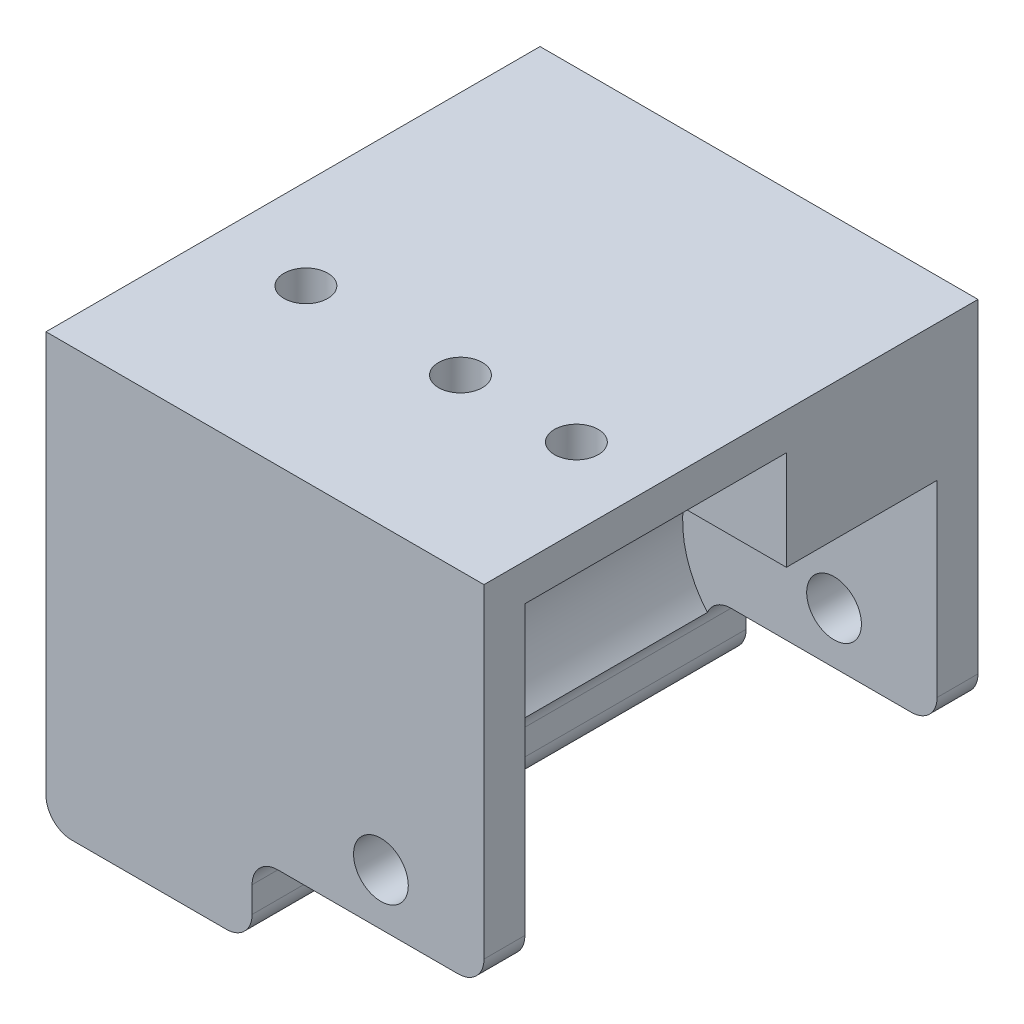
SolidWorks part; units mm, degrees
ref_plane "Front Plane" through (0, 0, 0) normal (0, 0, 1) x (1, 0, 0)
ref_plane "Top Plane" through (0, 0, 0) normal (0, 1, 0) x (1, 0, 0)
ref_plane "Right Plane" through (0, 0, 0) normal (1, 0, 0) x (0, 0, -1)
sketch "Sketch1" plane through (0, 0, 0) normal (0, 0, 1) x (1, 0, 0)
  line L0 (-18, 24) -> (-18, 0) construction
  line L5 (0, 0) -> (-18, 0)
  line L6 (0, 0) -> (0, 24)
  line L7 (0, 24) -> (-34, 24)
  line L8 (-34, 0) -> (-34, 24)
  line L11 (-34, 0) -> (-34, -6)
  line L12 (-34, -6) -> (-18, -6)
  line L13 (-18, 0) -> (-18, -6)
  circle A27 centre (-4, 19.15) radius 2.125 construction
  circle A28 centre (-12, 19.15) radius 2.125 construction
  circle A29 centre (-21, 19.15) radius 2.125 construction
  circle A30 centre (-8, 4) radius 2.125
  dimension "D3" = 4.25
  dimension "D7" = 8
  dimension "D8" = 4.25
  dimension "D1" = 4.25
  dimension "D2" = 4.25
  dimension "D4" = 4.85
  dimension "D5" = 9
  dimension "D9" = 4
  dimension "D6" = 4
  dimension "D10" = 4
  dimension "D11" = 24
  dimension "D12" = 13
  dimension "D13" = 16
  dimension "D14" = 30
extrude "Boss-Extrude1" add sketch "Sketch1" along normal blind 3.175
ref_plane "Plane1" through (0, 0, -16) normal (0, 0, -1) x (-1, 0, 0)
sketch "Sketch4" plane through (0, 24, 0) normal (0, 1, 0) x (1, 0, 0)
  line L0 (-34, 32) -> (0, 32) construction
  line L1 (-34, -3.175) -> (0, -3.175)
  line L2 (-34, -3.175) -> (-34, 35.175)
  line L3 (-34, 35.175) -> (0, 35.175)
  line L4 (0, -3.175) -> (0, 35.175)
  line L5 (0, 0) -> (-34, 0) construction
  dimension "D1" = 3.175
  dimension "D2" = 32
extrude "Boss-Extrude2" add sketch "Sketch4" along normal blind 3.175
mirror "Mirror2" about plane through (0, 0, -16) normal (0, 0, -1) of "Boss-Extrude1"
sketch "Sketch5" plane through (0, 0, 0) normal (0, 0, -1) x (-1, 0, 0)
  line L0 (0, 24) -> (34, 24) construction
  line L1 (0, 24) -> (34, 24) construction
  line L2 (18, 9) -> (18, 16.6)
  line L3 (34, -6) -> (18, -6)
  line L4 (34, -6) -> (34, 16.6)
  line L6 (18, -6) -> (18, -1)
  line L7 (18, 16.6) -> (34, 16.6)
  arc A1 (18, -1) -> (18, 9) centre (11.755, 4) ccw
  point P3 (0, 0)
  dimension "D3" = 8
  dimension "D1" = 16
  dimension "D2" = 5
  dimension "D4" = 10
  dimension "D5" = 22.6
  dimension "D6" = 0
extrude "Boss-Extrude3" add sketch "Sketch5" along normal up to next
sketch "Sketch6" plane through (0, 0, -32) normal (0, 0, 1) x (1, 0, 0)
  line L0 (0, 0) -> (0, 27.175) construction
  line L1 (-34, 24) -> (0, 24)
  line L2 (-34, 24) -> (-34, 16.6)
  line L3 (-34, 16.6) -> (0, 16.6)
  line L4 (0, 24) -> (0, 16.6)
  dimension "D1" = 7.4
extrude "Boss-Extrude4" add sketch "Sketch6" along normal blind 11.7
fillet "Fillet1" radius 2 5 edges at (-18, 0, 1.5875) (0, 0, -33.5875) (0, 0, 1.5875) (-34, -6, -16) (-18, -6, -16)
sketch "Sketch7" plane through (0, 24, 0) normal (0, -1, 0) x (1, 0, 0)
  line L4 (-34, -20.3) -> (0, -20.3)
  line L5 (0, -20.3) -> (0, 0)
  line L6 (0, 0) -> (-34, 0)
  line L7 (-34, 0) -> (-34, -20.3)
  line L8 (-34, -20.3) -> (0, -20.3)
  line L9 (0, -20.3) -> (0, 0)
  line L10 (0, 0) -> (-34, 0)
  line L11 (-34, 0) -> (-34, -20.3)
  dimension "D1" = 0
extrude "Cut-Extrude1" cut sketch "Sketch7" against normal blind 0.3
sketch "Sketch8" plane through (0, 27.175, 0) normal (0, 1, 0) x (1, 0, 0)
  line L0 (0, 0) -> (-34, 0) construction
  line L1 (-34, 20.3) -> (0, 20.3) construction
  line L2 (0, 0) -> (-34, 0) construction
  line L3 (-34, 20.3) -> (0, 20.3) construction
  line L4 (-34, 10) -> (0, 10) construction
  line L5 (-34, 35.175) -> (-34, -3.175) construction
  line L6 (0, -3.175) -> (0, 35.175) construction
  circle A0 centre (-15, 10) radius 1.7
  circle A1 centre (-27, 10) radius 1.7
  circle A2 centre (-6, 10) radius 1.7
  dimension "D3" = 3.4
  dimension "D4" = 3.4
  dimension "D6" = 3.4
  dimension "D1" = 10
  dimension "D2" = 15
  dimension "D5" = 12
  dimension "D7" = 9
extrude "Cut-Extrude2" cut sketch "Sketch8" against normal through all
